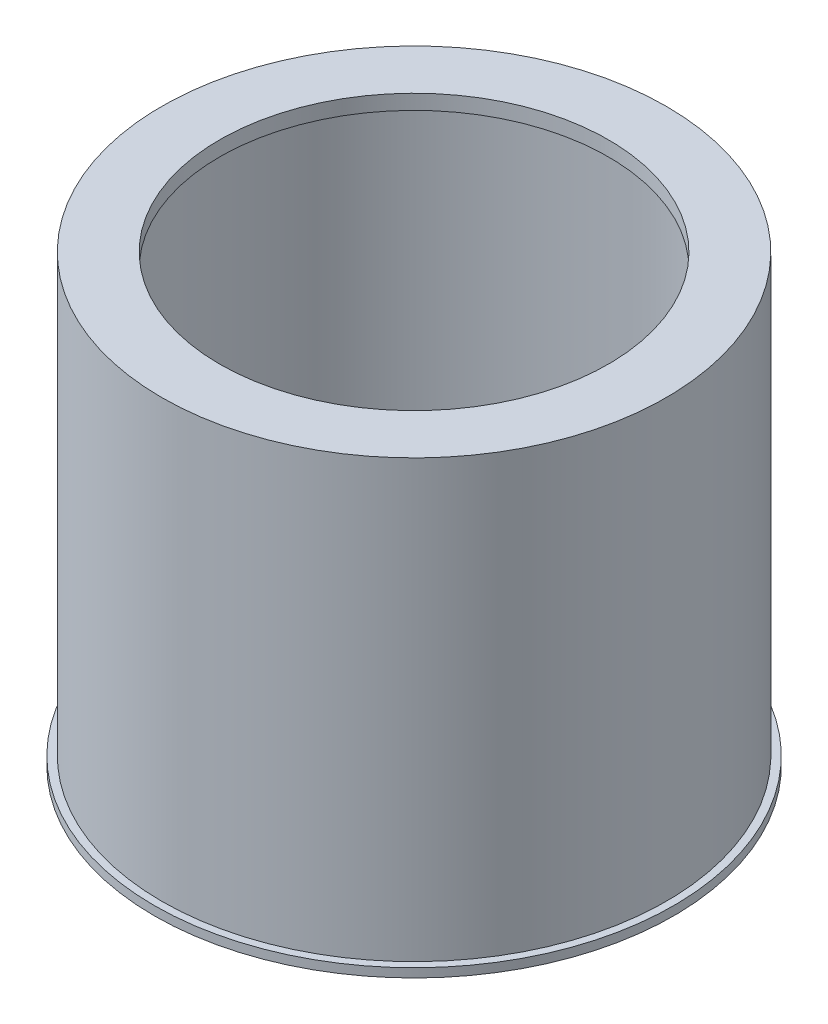
SolidWorks part; units mm, degrees
ref_plane "Front Plane" through (0, 0, 0) normal (0, 0, 1) x (1, 0, 0)
ref_plane "Top Plane" through (0, 0, 0) normal (0, 1, 0) x (1, 0, 0)
ref_plane "Right Plane" through (0, 0, 0) normal (1, 0, 0) x (0, 0, -1)
sketch "Receptacle Floor Sketch" plane through (0, 0, 0) normal (0, 1, 0) x (1, 0, 0)
  circle A0 centre (0, 0) radius 175
  circle A1 centre (0, 0) radius 12.5
  dimension "D1" = 350
  dimension "D2" = 25
extrude "Receptacle Floor" add sketch "Receptacle Floor Sketch" along normal blind 6
sketch "Receptacle Wall Sketch" plane through (0, 0, 0) normal (0, 1, 0) x (1, 0, 0)
  circle A0 centre (0, 0) radius 170
  circle A1 centre (0, 0) radius 166
  dimension "D1" = 340
  dimension "D2" = 332
extrude "Receptacle Wall" add sketch "Receptacle Wall Sketch" along normal blind 300
sketch "Pot Seat Ledge Sketch" plane through (0, 0, 0) normal (0, 1, 0) x (1, 0, 0)
  circle A0 centre (0, 0) radius 167
  circle A1 centre (0, 0) radius 131
  dimension "D1" = 334
  dimension "D2" = 262
extrude "Pot Seat Ledge" add sketch "Pot Seat Ledge Sketch" along normal blind 10 from offset 290
